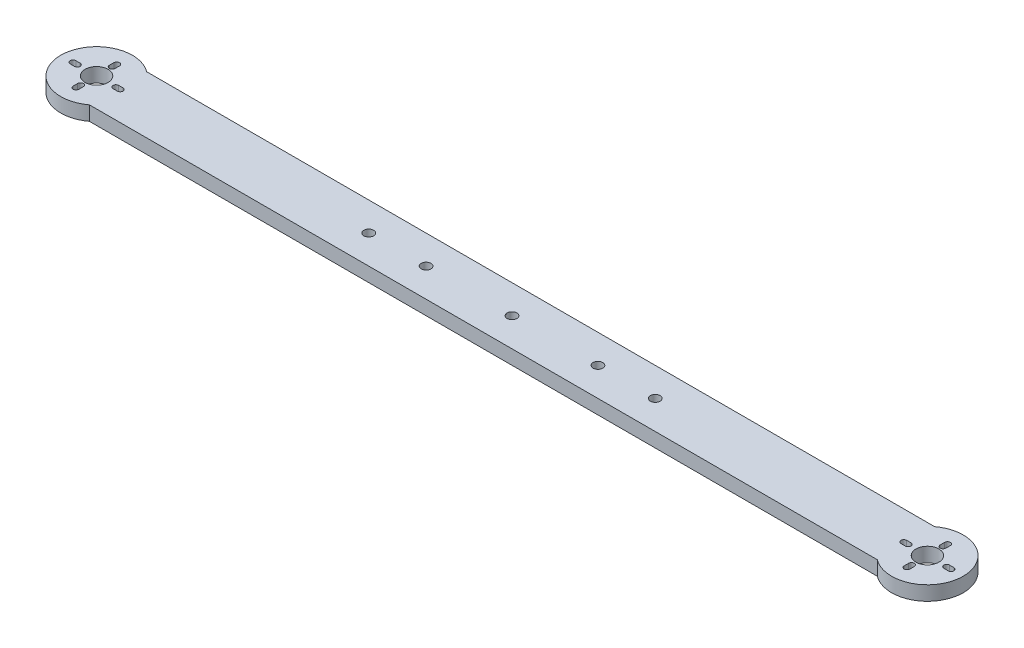
SolidWorks part; units mm, degrees
material "Thornel Mat VMA"
ref_plane "Front Plane" through (0, 0, 0) normal (0, 0, 1) x (1, 0, 0)
ref_plane "Top Plane" through (0, 0, 0) normal (0, 1, 0) x (1, 0, 0)
ref_plane "Right Plane" through (0, 0, 0) normal (1, 0, 0) x (0, 0, -1)
sketch "Sketch1" plane through (0, 0, 0) normal (0, 1, 0) x (1, 0, 0)
  line L0 (0, 12.7) -> (0, -12.7) construction
  line L1 (-174.625, 12.7) -> (174.625, 12.7)
  line L3 (-174.625, -12.7) -> (174.625, -12.7)
  arc A0 (-174.625, 12.7) -> (-174.625, -12.7) centre (-184.15, 0) ccw
  arc A1 (174.625, -12.7) -> (174.625, 12.7) centre (184.15, 0) ccw
  point P8 (0, 12.7)
  point P12 (0, 0)
  dimension "D3" = 31.75
  dimension "D4" = 31.75
extrude "Boss-Extrude1" add sketch "Sketch1" along normal blind 6.35
sketch "Sketch2" plane through (0, 6.35, 0) normal (0, 1, 0) x (1, 0, 0)
  line L0 (173.6914, 0) -> (175.6086, 0) construction
  line L1 (173.6914, 1.25) -> (175.6086, 1.25)
  line L2 (173.6914, -1.25) -> (175.6086, -1.25)
  line L3 (184.15, 0) -> (184.15, 3.2374) construction
  line L4 (194.6086, 0) -> (192.6914, 0) construction
  line L5 (194.6086, 1.25) -> (192.6914, 1.25)
  line L6 (194.6086, -1.25) -> (192.6914, -1.25)
  line L7 (184.15, 8.9209) -> (184.15, 6.921) construction
  line L8 (185.4, 8.9209) -> (185.4, 6.921)
  line L9 (182.9, 8.9209) -> (182.9, 6.921)
  line L10 (184.1914, -9.079) -> (184.1914, -7.079) construction
  line L11 (185.4414, -9.079) -> (185.4414, -7.079)
  line L12 (182.9414, -9.079) -> (182.9414, -7.079)
  line L13 (0, 0) -> (184.15, 0) construction
  line L14 (0, 0) -> (0, 12.7) construction
  line L15 (174.625, 12.7) -> (-174.625, 12.7) construction
  line L16 (-184.15, 0) -> (-184.15, 3.2374) construction
  line L17 (-184.1914, -9.079) -> (-184.1914, -7.079) construction
  line L18 (-185.4414, -9.079) -> (-185.4414, -7.079)
  line L19 (-182.9414, -9.079) -> (-182.9414, -7.079)
  line L20 (-184.15, 8.9209) -> (-184.15, 6.921) construction
  line L21 (-185.4, 8.9209) -> (-185.4, 6.921)
  line L22 (-182.9, 8.9209) -> (-182.9, 6.921)
  line L23 (-194.6086, 0) -> (-192.6914, 0) construction
  line L24 (-194.6086, 1.25) -> (-192.6914, 1.25)
  line L25 (-194.6086, -1.25) -> (-192.6914, -1.25)
  line L26 (-173.6914, 0) -> (-175.6086, 0) construction
  line L27 (-173.6914, 1.25) -> (-175.6086, 1.25)
  line L28 (-173.6914, -1.25) -> (-175.6086, -1.25)
  circle A0 centre (184.15, 0) radius 5.08
  arc A1 (173.6914, 1.25) -> (173.6914, -1.25) centre (173.6914, 0) ccw
  arc A2 (175.6086, -1.25) -> (175.6086, 1.25) centre (175.6086, 0) ccw
  arc A3 (194.6086, 1.25) -> (194.6086, -1.25) centre (194.6086, 0) cw
  arc A4 (192.6914, -1.25) -> (192.6914, 1.25) centre (192.6914, 0) cw
  arc A5 (185.4, 8.9209) -> (182.9, 8.9209) centre (184.15, 8.9209) ccw
  arc A6 (182.9, 6.921) -> (185.4, 6.921) centre (184.15, 6.921) ccw
  arc A7 (185.4414, -9.079) -> (182.9414, -9.079) centre (184.1914, -9.079) cw
  arc A8 (182.9414, -7.079) -> (185.4414, -7.079) centre (184.1914, -7.079) cw
  circle A9 centre (-184.15, 0) radius 5.08
  arc A10 (-185.4414, -9.079) -> (-182.9414, -9.079) centre (-184.1914, -9.079) ccw
  arc A11 (-182.9414, -7.079) -> (-185.4414, -7.079) centre (-184.1914, -7.079) ccw
  arc A12 (-185.4, 8.9209) -> (-182.9, 8.9209) centre (-184.15, 8.9209) cw
  arc A13 (-182.9, 6.921) -> (-185.4, 6.921) centre (-184.15, 6.921) cw
  arc A14 (-194.6086, 1.25) -> (-194.6086, -1.25) centre (-194.6086, 0) ccw
  arc A15 (-192.6914, -1.25) -> (-192.6914, 1.25) centre (-192.6914, 0) ccw
  arc A16 (-173.6914, 1.25) -> (-173.6914, -1.25) centre (-173.6914, 0) cw
  arc A17 (-175.6086, -1.25) -> (-175.6086, 1.25) centre (-175.6086, 0) cw
  point P4 (174.65, 0)
  point P12 (193.65, 0)
  point P19 (184.15, 7.921)
  point P26 (184.1914, -8.079)
  point P41 (-184.1914, -8.079)
  point P48 (-184.15, 7.921)
  point P55 (-193.65, 0)
  point P62 (-174.65, 0)
  dimension "D4" = 10.16
  dimension "D1" = 16
  dimension "D2" = 19
  dimension "D3" = 184.15
  dimension "D5" = 1.9999
extrude "Cut-Extrude1" cut sketch "Sketch2" against normal through all
sketch "Sketch3" plane through (0, 6.35, 0) normal (0, 1, 0) x (1, 0, 0)
  circle A0 centre (0, 0) radius 2.159
  circle A1 centre (38.1, 0) radius 2.159
  circle A2 centre (-38.1, 0) radius 2.159
  dimension "D1" = 38.1
  dimension "D3" = 4.318
  dimension "D4" = 4.318
  dimension "D5" = 4.318
  dimension "D2" = 38.1
extrude "Cut-Extrude2" cut sketch "Sketch3" against normal through all
sketch "Sketch4" plane through (0, 6.35, 0) normal (0, 1, 0) x (1, 0, 0)
  line L0 (0, 12.7) -> (0, -33.8789) construction
  line L1 (174.625, 12.7) -> (-174.625, 12.7) construction
  circle A0 centre (63.5, 0) radius 2.159
  circle A1 centre (184.15, 0) radius 5.08 construction
  circle A2 centre (-63.5, 0) radius 2.159
  dimension "D1" = 4.318
  dimension "D2" = 120.65
extrude "Cut-Extrude3" cut sketch "Sketch4" against normal through all
